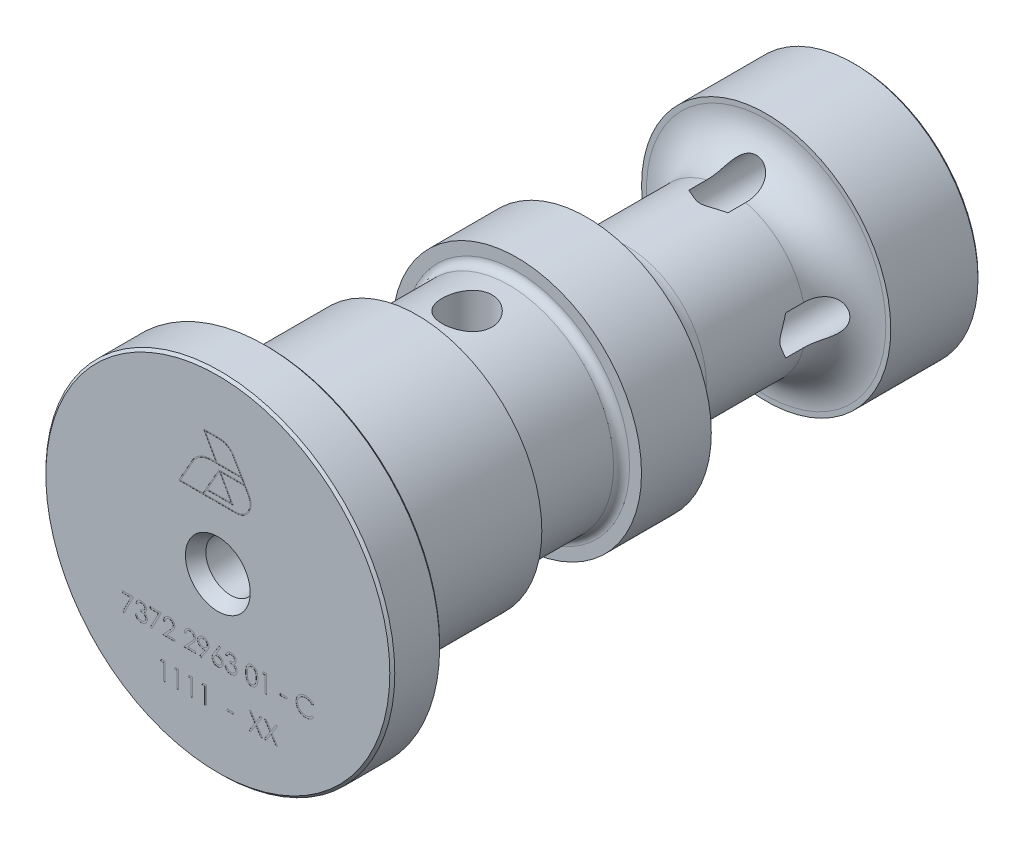
SolidWorks part; units mm, degrees
material "17CrNiMo6"
ref_plane "Front Plane" through (0, 0, 0) normal (0, 0, 1) x (1, 0, 0)
ref_plane "Top Plane" through (0, 0, 0) normal (0, 1, 0) x (1, 0, 0)
ref_plane "Right Plane" through (0, 0, 0) normal (1, 0, 0) x (0, 0, -1)
ref_axis "Axis1" through (0, 0, -67.2) along (0, 0, 1)
sketch "Sketch1" plane through (0, 0, 0) normal (1, 0, 0) x (0, 0, -1)
  line L0 (-67.4987, 0) -> (155.582, 0) construction
  line L1 (0, 3.25) -> (0, 17.25)
  line L2 (0.25, 17.5) -> (4.75, 17.5)
  line L3 (5, 17.25) -> (5, 14.4975)
  line L4 (7, 12.4975) -> (20, 12.4975)
  line L5 (20, 12.4975) -> (20, 11.3)
  line L6 (20.8, 10.5) -> (29.2, 10.5)
  line L7 (30, 11.3) -> (30, 12.4975)
  line L8 (30, 12.4975) -> (37, 12.4975)
  line L9 (37, 12.4975) -> (37, 12)
  line L10 (41, 8) -> (51, 8)
  line L11 (55, 12) -> (55, 12.4975)
  line L12 (55, 12.4975) -> (63.75, 12.4975)
  line L13 (64, 12.2475) -> (64, 10)
  line L14 (63.5, 9.5) -> (60.25, 9.5)
  line L15 (59, 8.25) -> (59, 4.25)
  line L16 (57.7183, 3.51) -> (33, 3.51)
  line L17 (22.0429, 3.4) -> (20, 0)
  line L18 (20, 0) -> (11, 0)
  line L19 (64, 10) -> (63.5, 9.5)
  line L20 (59, 4.25) -> (57.7183, 3.51)
  line L21 (1.299, 2.5) -> (9.4978, 2.5)
  line L22 (9.4978, 2.5) -> (11, 0)
  line L23 (22.0429, 3.4) -> (33, 3.4)
  line L24 (33, 3.4) -> (33, 3.51)
  line L25 (0, 3.25) -> (1.299, 2.5)
  line L26 (4.75, 17.5) -> (5, 17.25)
  line L27 (0, 17.25) -> (0.25, 17.5)
  line L28 (63.75, 12.4975) -> (64, 12.2475)
  arc A0 (7, 12.4975) -> (5, 14.4975) centre (7, 14.4975) cw
  arc A1 (20.8, 10.5) -> (20, 11.3) centre (20.8, 11.3) cw
  arc A2 (30, 11.3) -> (29.2, 10.5) centre (29.2, 11.3) cw
  arc A3 (41, 8) -> (37, 12) centre (41, 12) cw
  arc A4 (55, 12) -> (51, 8) centre (51, 12) cw
  arc A5 (60.25, 9.5) -> (59, 8.25) centre (60.25, 8.25) ccw
  point P4 (0, 17.5)
  point P5 (5, 17.5)
  point P15 (64, 12.4975)
  point P16 (64, 9.5)
  point P18 (59, 3.51)
  point P29 (37, 8)
  point P32 (55, 8)
  point P39 (59, 9.5)
  dimension "D18" = 2
  dimension "D19" = 0.8
  dimension "D20" = 4
  dimension "D25" = 1.25
  dimension "D1" = 35
  dimension "D4" = 24.995
  dimension "D5" = 59
  dimension "D6" = 9
  dimension "D7" = 21
  dimension "D8" = 27
  dimension "D9" = 34
  dimension "D10" = 16
  dimension "D11" = 44
  dimension "D12" = 6.8
  dimension "D13" = 19
  dimension "D14" = 5
  dimension "D15" = 7.02
  dimension "D16" = 44
  dimension "D17" = 59
  dimension "D21" = 0.5
  dimension "D22" = 45
  dimension "D23" = 8.5
  dimension "D24" = 30
  dimension "D26" = 5
  dimension "D27" = 31
  dimension "D28" = 30
  dimension "D29" = 64
  dimension "D30" = 59
  dimension "D31" = 11
  dimension "D32" = 6.5
revolve "Revolve1" add sketch "Sketch1" angle 360 about L0
cosmetic thread "Cosmetic Thread1" parameters "D1"=8, "D2"=6
sketch "Sketch2" plane through (0, 0, -64) normal (0, 0, -1) x (-1, 0, 0)
  circle A0 centre (0, 7.375) radius 2
  circle A2 centre (0, 0) radius 7.375 construction
  circle A3 centre (7.375, 0) radius 2
  circle A4 centre (0, -7.375) radius 2
  circle A5 centre (-7.375, 0) radius 2
  dimension "D1" = 4
  dimension "D4" = 14.75
sketch "Sketch3" plane through (0, 0, 0) normal (1, 0, 0) x (0, 0, -1)
  line L0 (68.054, -7.375) -> (42.7995, -7.375) construction
  line L1 (66.8184, -7.375) -> (66.8184, -9.375)
  line L2 (66.8184, -9.375) -> (49.2017, -9.375)
  line L3 (49.2017, -9.375) -> (48, -7.375)
  line L4 (48, -7.375) -> (66.8184, -7.375)
  point P7 (64, -7.375)
  dimension "D1" = 4
  dimension "D2" = 59
  dimension "D3" = 16
revolve "Cut-Revolve3" cut sketch "Sketch3" angle 360 about L0
pattern_circular "CirPattern1" count 4 over 360 about axis through (0, 0, -67.2) along (0, 0, 1) of "Cut-Revolve3"
sketch "Sketch4" plane through (0, 0, 0) normal (0, 1, 0) x (1, 0, 0)
  line L0 (10, 64) -> (-10, 64) construction
  circle A0 centre (0, 25) radius 2.5
  dimension "D1" = 5
  dimension "D2" = 39
extrude "Cut-Extrude2" cut sketch "Sketch4" against normal through all and the other way through all
sketch "Sketch5" plane through (0, 0, 0) normal (0, 0, 1) x (1, 0, 0)
  line L0 (-11.1939, -8.0213) -> (11.1939, -8.0213) construction
  line L1 (0, 0) -> (0, -8.0213) construction
  line L2 (-4.8311, 6.1915) -> (4.6158, 6.1915) construction
  text T0 "7372 2963 01 - C\r\n1111  -  XX" font "Century Gothic" height 1.8
  line B0 (1.8412, 6.1915) -> (-1.4272, 6.1915)
  line B1 (1.3571, 6.8578) -> (-1.0483, 6.8578)
  line B2 (-1.3703, 6.2915) -> (-1.1052, 6.7578)
  line B3 (-0.1692, 9.6357) -> (-0.7392, 9.6357)
  line B4 (-1.4272, 11.8997) -> (-0.1692, 9.6357)
  line B5 (1.3571, 6.8578) -> (0.1727, 9.005)
  line B6 (2.8021, 9.005) -> (3.1009, 8.4886)
  line B7 (0.1768, 11.8997) -> (-1.4272, 11.8997)
  line B8 (2.4581, 9.6357) -> (2.8021, 9.005)
  line B9 (2.4581, 9.6357) -> (1.5943, 11.0923)
  line B10 (-1.4272, 6.1915) -> (-3.9246, 6.1915)
  line B11 (-2.5206, 8.6607) -> (-3.9246, 6.1915)
  line B12 (2.6564, 9.1054) -> (2.4012, 9.5357)
  line B13 (0.1768, 11.7997) -> (-1.2572, 11.7997)
  line B14 (-1.2572, 11.7997) -> (-0.0548, 9.6357)
  line B15 (-0.7392, 9.5357) -> (2.4012, 9.5357)
  line B16 (-2.4349, 8.609) -> (-3.7527, 6.2915)
  line B17 (-1.4854, 6.2915) -> (-3.7527, 6.2915)
  line B18 (0.1147, 9.1054) -> (2.6564, 9.1054)
  line B19 (-1.4854, 6.2915) -> (0.1147, 9.1054)
  line B20 (2.6866, 9.005) -> (3.0154, 8.4367)
  line B21 (1.8412, 6.2915) -> (-1.3703, 6.2915)
  line B22 (-0.0548, 9.6357) -> (2.3419, 9.6357)
  line B23 (2.3419, 9.6357) -> (1.5083, 11.0413)
  line B24 (1.5265, 6.7578) -> (-1.1052, 6.7578)
  line B25 (1.5265, 6.7578) -> (0.2869, 9.005)
  line B26 (0.2869, 9.005) -> (2.6866, 9.005)
  line B27 (-1.0483, 6.8578) -> (0.1727, 9.005)
  arc B28 (1.5943, 11.0923) -> (0.1768, 11.8997) centre (0.1768, 10.2517) ccw
  arc B29 (1.8412, 6.1915) -> (3.1009, 8.4886) centre (1.8412, 7.6854) ccw
  arc B30 (-0.7392, 9.6357) -> (-2.5206, 8.6607) centre (-0.7392, 7.5211) ccw
  arc B31 (1.5083, 11.0413) -> (0.1768, 11.7997) centre (0.1768, 10.2517) ccw
  arc B32 (-0.7392, 9.5357) -> (-2.4349, 8.609) centre (-0.7392, 7.5211) ccw
  arc B33 (1.8412, 6.2915) -> (3.0154, 8.4367) centre (1.8412, 7.6854) ccw
  dimension "D1" = 8.0213
  dimension "D2" = 6.1915
sketch_block_instance "SKETCH LOGO-1"
sketch_block "SKETCH LOGO" parameters "D1"=29.059, "D2"=11.4163, "D3"=29.624, "D4"=6.8884
extrude "Cut-Extrude3" cut sketch "Sketch5" against normal blind 0.01
